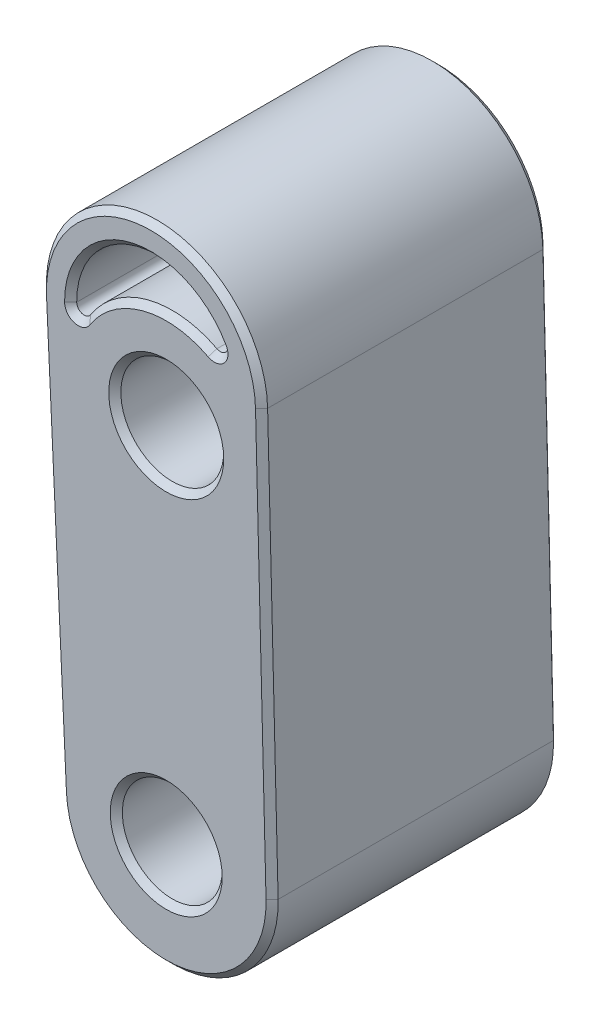
SolidWorks part; units mm, degrees
ref_plane "Front" through (0, 0, 0) normal (0, 0, 1) x (1, 0, 0)
ref_plane "Top" through (0, 0, 0) normal (0, 1, 0) x (1, 0, 0)
ref_plane "Right" through (0, 0, 0) normal (1, 0, 0) x (0, 0, -1)
sketch "Sketch1" plane through (0, 0, 0) normal (0, 0, 1) x (1, 0, 0)
  line L3 (-3.2, 0) -> (-1.6, 0) construction
  line L23 (1.65, -12) -> (3.25, -12) construction
  line L33 (-3.199, 0.08) -> (-3.4989, -11.9125)
  line L34 (3.4989, -11.9125) -> (3.199, 0.08)
  circle A0 centre (0, 0) radius 3.2 construction
  circle A3 centre (0, 0) radius 1.6
  circle A12 centre (0, -12) radius 1.65
  circle A13 centre (0, -12) radius 4.25 construction
  arc A22 (-3.199, 0.08) -> (3.199, 0.08) centre (0, 0) cw
  arc A28 (-3.4989, -11.9125) -> (3.4989, -11.9125) centre (0, -12) ccw
  dimension "D1" = 3.2
  dimension "D3" = 8.5
  dimension "D6" = 3.3
  dimension "D7" = 3.5
  dimension "D2" = 1.6
  dimension "D5" = 12
extrude "Boss-Extrude1" add sketch "Sketch1" along normal mid plane 9.5 contours A3 region at (0, -6.3007, 0)
sketch "Sketch2" plane through (0, 0, 0) normal (0, 0, 1) x (1, 0, 0)
  line L0 (-3.4961, -12.1661) -> (-4.1551, 1.7042)
  line L1 (0, 0) -> (0, 8.0844) construction
  line L2 (0, 0) -> (-0.5031, 1.8777) construction
  line L3 (-0.5031, 1.8777) -> (-1.2941, 4.8296) construction
  line L4 (-1.2941, 4.8296) -> (-1.4494, 5.4092) construction
  line L5 (3.1518, 1.9691) -> (3.4989, -11.9125)
  line L6 (3.4989, -11.9125) -> (3.199, 0.08) construction
  line L7 (3.4989, -11.9125) -> (3.199, 0.08) construction
  arc A0 (-4.1551, 1.7042) -> (3.1518, 1.9691) centre (-0.5031, 1.8777) cw
  circle A1 centre (0, 0) radius 5 construction
  arc A2 (-3.4989, -11.9125) -> (3.4989, -11.9125) centre (0, -12) ccw construction
  dimension "D2" = 10
  dimension "D1" = 0.6
  dimension "D3" = 15
extrude "Spring" add sketch "Sketch2" along normal through all and the other way through all thin thin type one direction wall 1
fillet "Spring Inside Fillets" radius 0.25 2 edges at (2.0977, 2.4166, 0) (-3.109, 0.7579, 0)
sketch "Sketch6" plane through (0, 0, 0) normal (0, 0, 1) x (1, 0, 0)
  line L0 (0, 0) -> (-0.3075, 1.5702) construction
  line L1 (-0.3075, 1.5702) -> (-0.3267, 1.6683) construction
  circle A0 centre (0, 0) radius 1.7
  circle A1 centre (0, 0) radius 1.6 construction
  dimension "D1" = 0.1
extrude "Loosen Top Joint" cut sketch "Sketch6" against normal through all both and the other way through all
chamfer "Deburs" distance 0.2 angle 45 20 edges at (1.65, -12, -4.75) (-1.1906, 4.4433, -4.75) (1.7718, 2.887, -4.75) (0.1268, -15.4977, -4.75) (-0.8282, 3.091, -4.75) (-0.6356, 5.5314, -4.75) (-3.8256, -5.2309, -4.75) (1.65, -12, 4.75) (1.7718, 2.887, 4.75) (-1.1906, 4.4433, 4.75) (-0.6356, 5.5314, 4.75) (-0.8282, 3.091, 4.75) (0.1268, -15.4977, 4.75) (-3.8256, -5.2309, 4.75) (-2.9779, 1.6144, -4.75) (-2.9779, 1.6144, 4.75) (3.3253, -4.9717, -4.75) (3.3253, -4.9717, 4.75) (1.7, 0, -4.75) (1.7, 0, 4.75)
sketch "Sketch3" plane through (-4.0649, -0.1931, 0) normal (-0.9989, -0.0475, 0) x (0, 0, 1)
  line L1 (0, -0.6005) -> (0, -9.4865) construction
  line L6 (4.55, 1.8995) -> (-4.55, 1.8995) construction
  line L8 (4.55, -11.9865) -> (-4.55, -11.9865) construction
  dimension "D1" = 2.5
  dimension "D2" = 2.5
sketch "Sketch4" plane through (-4.0649, -0.1931, 0) normal (-0.9989, -0.0475, 0) x (0, 0, 1)
  line L0 (0, -0.6005) -> (0, -9.4865)
  line L1 (-2, -2.6005) -> (0, -0.6005)
  line L2 (0, -0.6005) -> (2, -2.6005)
  line L3 (0, -0.6005) -> (0, -9.4865) construction
  line L6 (0, -12.0651) -> (0, -0.0719) construction
  dimension "D1" = 45
  dimension "D2" = 2
extrude "Arrow Point" add sketch "Sketch4" along normal blind 0.2 draft 55 thin contours L1 | L2 thin type one direction wall 0.8
sketch "Sketch5" plane through (-4.0649, -0.1931, 0) normal (-0.9989, -0.0475, 0) x (0, 0, 1)
  line L0 (0, -1.0045) -> (0, -9.4865)
  line L1 (0, -0.6005) -> (0, -9.4865) construction
extrude "Arrow Shaft" add sketch "Sketch5" along normal blind 0.2 draft 55 thin thin type mid plane wall 0.8
chamfer "Deburs no Spring" [suppressed] distance 0.2 angle 45
equation "\"D1@Sketch1\"=\"Clearance Hole Diameter@Box Assy.Assembly\"+.05mm"
equation "\"D6@Sketch1\"=\"Clearance Hole Diameter@Box Assy.Assembly\"+.15mm"
